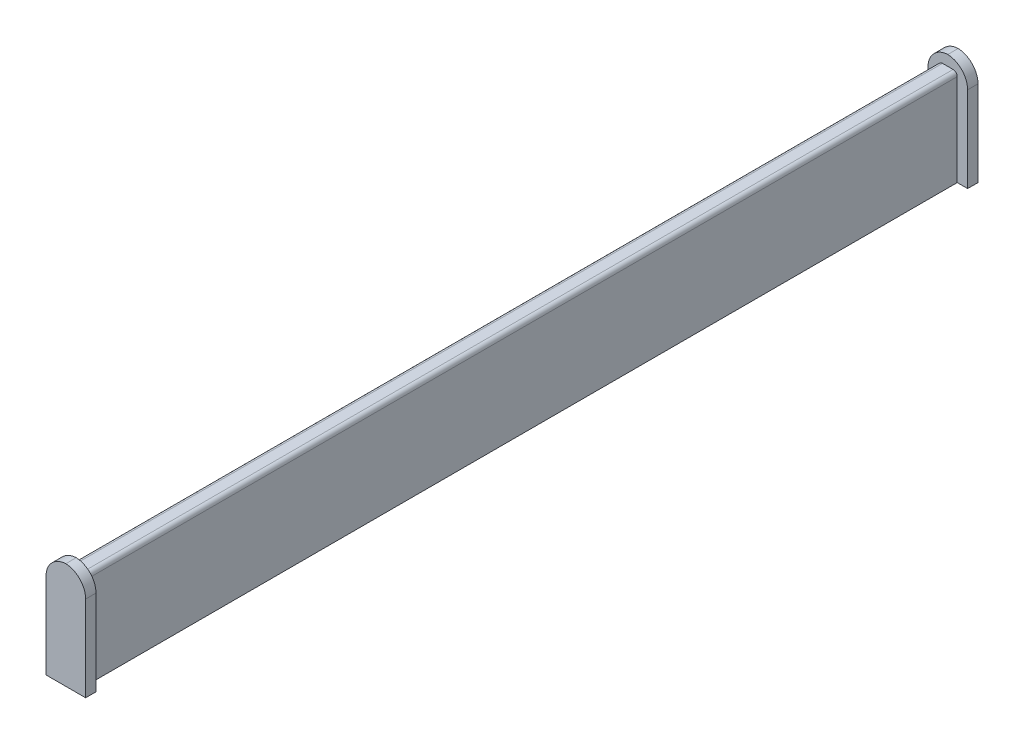
SolidWorks part; units mm, degrees
ref_plane "Front Plane" through (0, 0, 0) normal (0, 0, 1) x (1, 0, 0)
ref_plane "Top Plane" through (0, 0, 0) normal (0, 1, 0) x (1, 0, 0)
ref_plane "Right Plane" through (0, 0, 0) normal (1, 0, 0) x (0, 0, -1)
sketch "Sketch1" plane through (0, 0, 0) normal (0, 0, 1) x (1, 0, 0)
  line L0 (0, 0) -> (0, 1.905)
  line L3 (0, 3.81) -> (3.175, 3.81)
  line L6 (3.175, 1.905) -> (3.175, 0)
  line L7 (3.175, 0) -> (0, 0)
  line L16 (0, 3.81) -> (0, 1.905)
  line L17 (3.175, 3.81) -> (3.175, 1.905)
  line L18 (0.1429, 3.6671) -> (3.0321, 3.6671)
  line L19 (3.0321, 3.6671) -> (3.0321, 1.905)
  line L20 (3.0321, 1.905) -> (3.0321, 0.1429)
  line L21 (3.0321, 0.1429) -> (0.1429, 0.1429)
  line L22 (0.1429, 0.1429) -> (0.1429, 1.905)
  line L23 (0.1429, 3.6671) -> (0.1429, 1.905)
  dimension "D1" = 3.175
  dimension "D2" = 0.1429
  dimension "D3" = 1.905
extrude "Boss-Extrude1" add sketch "Sketch1" along normal blind 133.35 contours L22 L23 L18 L19 L20 L21
ref_plane "Plane1" through (1.5875, 0, 0) normal (1, 0, 0) x (0, 0, -1)
ref_plane "Plane2" through (0, 0, 66.675) normal (0, 0, 1) x (1, 0, 0)
sketch "Sketch2" plane through (0, 0, 133.35) normal (0, 0, 1) x (1, 0, 0)
  line L0 (0.1429, 0.1429) -> (0.1429, 3.6671) construction
  line L1 (-1.4446, 0.1429) -> (4.6196, 0.1429)
  line L2 (-1.4446, 0.1429) -> (-1.4446, 5.2546)
  line L3 (-1.4446, 5.2546) -> (4.6196, 5.2546)
  line L4 (4.6196, 0.1429) -> (4.6196, 5.2546)
  line L5 (3.0321, 3.6671) -> (3.0321, 0.1429) construction
  line L6 (0.1429, 3.6671) -> (3.0321, 3.6671) construction
  dimension "D1" = 1.5875
  dimension "D2" = 1.5875
  dimension "D3" = 1.5875
extrude "Boss-Extrude2" add sketch "Sketch2" along normal blind 1.5875 contours L2 L1 L4 L3
fillet "Fillet1" radius 3.175 2 edges at (-1.4446, 5.2546, 134.1438) (4.6196, 5.2546, 134.1438)
mirror "Mirror1" about plane through (0, 0, 66.675) normal (0, 0, 1) of "Fillet1", "Boss-Extrude2"
fillet "Fillet2" radius 0.635 2 edges at (0.1429, 3.6671, 66.675) (3.0321, 3.6671, 66.675)
sketch "Sketch3" plane through (0, 0.1429, 0) normal (0, -1, 0) x (1, 0, 0)
  line L0 (-1.4446, 134.9375) -> (4.6196, 134.9375)
  line L1 (4.6196, 134.9375) -> (4.6196, 133.35)
  line L2 (4.6196, 133.35) -> (3.0321, 133.35)
  line L3 (3.0321, 133.35) -> (3.0321, 0)
  line L4 (3.0321, 0) -> (4.6196, 0)
  line L5 (4.6196, 0) -> (4.6196, -1.5875)
  line L6 (4.6196, -1.5875) -> (-1.4446, -1.5875)
  line L7 (-1.4446, -1.5875) -> (-1.4446, 0)
  line L8 (-1.4446, 0) -> (0.1429, 0)
  line L9 (0.1429, 0) -> (0.1429, 133.35)
  line L10 (0.1429, 133.35) -> (-1.4446, 133.35)
  line L11 (-1.4446, 133.35) -> (-1.4446, 134.9375)
extrude "Boss-Extrude3" add sketch "Sketch3" along normal blind 11.15
